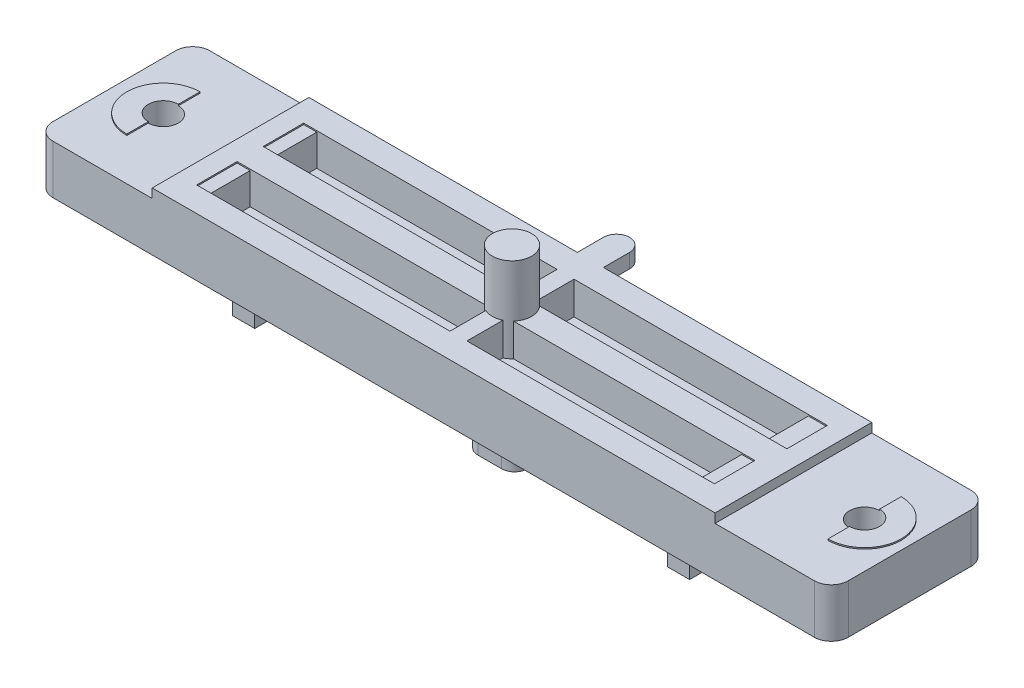
SolidWorks part; units mm, degrees
ref_plane "Alzado" through (0, 0, 0) normal (0, 0, 1) x (1, 0, 0)
ref_plane "Planta" through (0, 0, 0) normal (0, 1, 0) x (1, 0, 0)
ref_plane "Vista lateral" through (0, 0, 0) normal (1, 0, 0) x (0, 0, -1)
sketch "Croquis1" plane through (0, 0, 0) normal (0, 1, 0) x (1, 0, 0)
  line L0 (0, 0) -> (0, -12)
  line L1 (0, -12) -> (60.9, -12)
  line L2 (0, 0) -> (60.9, 0)
  line L3 (60.9, 0) -> (60.9, -12)
  dimension "D1" = 12
  dimension "D2" = 60.9
extrude "Saliente-Extruir1" add sketch "Croquis1" along normal blind 14
sketch "Croquis2" plane through (0, 14, 0) normal (0, 1, 0) x (1, 0, 0)
  line L0 (0, 0) -> (60.9, -12) construction
  circle A0 centre (30.45, -6) radius 1.5
  dimension "D1" = 3
extrude "Cortar-Extruir1" cut sketch "Croquis2" against normal blind 4 flip side to cut
sketch "Croquis3" plane through (0, 10, 0) normal (0, 1, 0) x (1, 0, 0)
  line L0 (30.45, -6) -> (30.45, 0) construction
  line L1 (60.9, 0) -> (0, 0) construction
  line L2 (30.45, 0) -> (29.45, 0)
  line L3 (29.45, 0) -> (29.45, 3)
  line L4 (29.45, 3) -> (31.45, 3)
  line L5 (31.45, 3) -> (31.45, 0)
  line L6 (31.45, 0) -> (30.45, 0)
  dimension "D1" = 1
  dimension "D2" = 2
  dimension "D3" = 3
extrude "Saliente-Extruir3" add sketch "Croquis3" against normal blind 1.1
sketch "Croquis4" plane through (0, 10, 0) normal (0, 1, 0) x (1, 0, 0)
  line L0 (30.45, -6) -> (8.9, -6) construction
  line L1 (8.9, -6) -> (8.9, 0)
  line L2 (29.45, 0) -> (0, 0) construction
  line L3 (8.9, 0) -> (29.45, 0)
  line L4 (60.9, 0) -> (31.45, 0) construction
  line L5 (52, 0) -> (52, -12)
  line L6 (0, -12) -> (60.9, -12) construction
  line L7 (52, -12) -> (8.9, -12)
  line L8 (8.9, -12) -> (8.9, -6)
  line L9 (29.45, 0) -> (29.45, 3)
  line L10 (29.45, 3) -> (31.45, 3)
  line L11 (31.45, 3) -> (31.45, 0)
  line L12 (31.45, 0) -> (52, 0)
  dimension "D1" = 21.55
  dimension "D2" = 43.1
extrude "Cortar-Extruir2" cut sketch "Croquis4" against normal blind 0.7 flip side to cut
sketch "Croquis5" plane through (0, 10, 0) normal (0, 1, 0) x (1, 0, 0)
  line L0 (52, -6) -> (49.5, -6) construction
  line L1 (52, -12) -> (52, 0) construction
  line L2 (49.05, -1.9) -> (49.05, -5)
  line L5 (49.05, -7) -> (49.05, -10.1)
  line L6 (49.05, -1.9) -> (31.1, -1.9)
  line L7 (49.05, -5) -> (31.568, -5)
  line L8 (49.05, -7) -> (31.568, -7)
  line L9 (49.05, -10.1) -> (31.1, -10.1)
  line L10 (30.45, -6) -> (30.45, -10.931) construction
  line L11 (31.1, -1.9) -> (31.1, -4.6481)
  line L12 (31.1, -7.3519) -> (31.1, -10.1)
  line L13 (29.8, -1.9) -> (11.4, -1.9)
  line L14 (11.4, -1.9) -> (11.4, -5)
  line L15 (11.4, -10.1) -> (29.8, -10.1)
  line L16 (29.332, -5) -> (11.4, -5)
  line L17 (8.9, 0) -> (8.9, -12) construction
  line L18 (11.4, -7) -> (29.332, -7)
  line L19 (11.4, -7) -> (11.4, -10.1)
  line L20 (29.8, -1.9) -> (29.8, -4.6481)
  line L21 (29.8, -7.3519) -> (29.8, -10.1)
  line L22 (30.45, -7) -> (31.568, -7)
  arc A0 (31.1, -7.3519) -> (31.568, -7) centre (30.45, -6) ccw
  arc A1 (31.568, -5) -> (31.1, -4.6481) centre (30.45, -6) ccw
  arc A2 (29.332, -7) -> (29.8, -7.3519) centre (30.45, -6) ccw
  arc A3 (31.1, -7.3519) -> (31.568, -7) centre (30.45, -6) ccw
  arc A4 (29.8, -4.6481) -> (29.332, -5) centre (30.45, -6) ccw
  arc A5 (31.568, -5) -> (31.1, -4.6481) centre (30.45, -6) ccw
  circle M22 centre (30.45, -6) radius 1.5
  dimension "D2" = 2.5
  dimension "D1" = 2.5
  dimension "D3" = 0.65
  dimension "D4" = 3.1
  dimension "D5" = 3.1
  dimension "D6" = 0.65
extrude "Cortar-Extruir3" cut sketch "Croquis5" against normal blind 2.5 contours L20 L13 L14 L16 M22 | L21 L18 L19 L15 M22 | L12 L9 L5 L8 M22 | L6 L11 L7 L2 M22 region at (40.0898, 10, 3.4476) region at (20.5851, 10, 3.4477) region at (40.0898, 10, 8.5524) region at (20.5851, 10, 8.5523)
sketch "Croquis6" plane through (0, 10, 0) normal (0, 1, 0) x (1, 0, 0)
  line L0 (49.05, -1.9) -> (50.5, -1.9)
  line L1 (49.05, -5) -> (50.5, -5)
  line L2 (50.5, -5) -> (50.5, -1.9)
  line L3 (52, -12) -> (52, 0) construction
  line L4 (49.05, -1.9) -> (49.05, -5)
  line L5 (50.05, -7) -> (50.05, -10.1)
  line L6 (11.4, -1.9) -> (10.4, -1.9)
  line L7 (49.05, -10.1) -> (49.05, -7)
  line L8 (49.05, -7) -> (50.05, -7)
  line L9 (49.05, -10.1) -> (50.05, -10.1)
  line L10 (10.4, -1.9) -> (10.4, -5)
  line L12 (11.4, -10.1) -> (11.4, -7)
  line L13 (8.9, 0) -> (8.9, -12) construction
  line L14 (11.4, -5) -> (10.4, -5)
  line L15 (11.4, -7) -> (10.4, -7)
  line L16 (11.4, -5) -> (11.4, -1.9)
  line L17 (10.4, -7) -> (10.4, -10.1)
  line L18 (11.4, -10.1) -> (10.4, -10.1)
  dimension "D1" = 1.5
  dimension "D2" = 1.5
extrude "Cortar-Extruir4" cut sketch "Croquis6" against normal blind 0.1
fillet "Redondeo1" radius 1 1 edges at (31.45, 9.45, -3)
fillet "Redondeo2" radius 1 1 edges at (29.45, 9.45, -3)
sketch "Croquis7" plane through (0, 9.3, 0) normal (0, 1, 0) x (1, 0, 0)
  line L0 (60.9, -6) -> (58.6, -6) construction
  line L1 (60.9, -12) -> (60.9, 0) construction
  line L2 (57.45, -8.8) -> (57.45, -7.15)
  line L3 (57.45, -4.85) -> (57.45, -3.2)
  line L6 (3.75, -4.85) -> (3.75, -3.2)
  line L7 (3.75, -7.15) -> (3.75, -8.8)
  arc A0 (57.45, -7.15) -> (57.45, -4.85) centre (57.45, -6) ccw
  arc A1 (57.45, -8.8) -> (57.45, -3.2) centre (57.45, -6) ccw
  arc A2 (3.75, -4.85) -> (3.75, -7.15) centre (3.75, -6) ccw
  arc A3 (3.75, -3.2) -> (3.75, -8.8) centre (3.75, -6) ccw
  dimension "D2" = 2.3
  dimension "D3" = 5.6
  dimension "D1" = 2.3
extrude "Saliente-Extruir4" add sketch "Croquis7" along normal blind 0.1 contours A3 L7 A2 L6 | A0 L3 A1 L2
sketch "Croquis8" plane through (0, 9.3, 0) normal (0, 1, 0) x (1, 0, 0)
  circle A0 centre (57.45, -6) radius 1.15
  circle A1 centre (3.75, -6) radius 1.15
extrude "Cortar-Extruir5" cut sketch "Croquis8" against normal up to next
sketch "Croquis9" plane through (0, 0, 0) normal (0, -1, 0) x (1, 0, 0)
  line L1 (30, 6) -> (30, 7.25)
  line L2 (30, 7.25) -> (28.1, 7.25)
  line L3 (28.1, 7.25) -> (28.1, 4.75)
  line L4 (28.1, 4.75) -> (31.9, 4.75)
  line L5 (31.9, 4.75) -> (31.9, 7.25)
  line L6 (31.9, 7.25) -> (30, 7.25)
  dimension "D1" = 1.9
  dimension "D2" = 1.25
  dimension "D3" = 3.8
  dimension "D4" = 2.5
extrude "Cortar-Extruir7" cut sketch "Croquis9" against normal blind 5.55 flip side to cut contours L2 L3 L4 L5 L6
sketch "Croquis10" plane through (0, 5.55, 0) normal (0, -1, 0) x (1, 0, 0)
  line L0 (29.35, 4.75) -> (30.65, 4.75)
  line L1 (31.9, 7.25) -> (28.1, 7.25) construction
  line L5 (45.8, 9.45) -> (45.8, 6.56) construction
  line L6 (30, 2.45) -> (47.5, 2.45)
  line L17 (14.2, 5.34) -> (14.2, 2.45) construction
  line L18 (29.35, 4.75) -> (29.35, 3.75)
  line L19 (29.35, 2.45) -> (30.65, 2.45)
  line L20 (30.65, 3.75) -> (30.65, 4.75)
  line L21 (28.1, 4.75) -> (29.35, 4.75)
  line L22 (30, 2.45) -> (12.5, 2.45)
  line L23 (47.5, 2.45) -> (47.5, 9.45)
  line L24 (14.2, 3.75) -> (29.35, 3.75)
  line L25 (12.5, 2.45) -> (12.5, 9.45)
  line L26 (12.5, 9.45) -> (14.2, 9.45)
  line L27 (47.5, 9.45) -> (45.8, 9.45)
  line L30 (30.65, 4.75) -> (31.9, 4.75)
  line L31 (30.65, 3.75) -> (45.8, 3.75)
  line L32 (14.2, 9.45) -> (14.2, 6.56) construction
  line L34 (45.8, 9.45) -> (45.8, 6.56)
  line L35 (14.2, 9.45) -> (14.2, 6.56)
  line L36 (15.8, 5.95) -> (15.8, 6.56)
  line L37 (15.8, 6.56) -> (14.2, 6.56)
  line L39 (14.2, 5.34) -> (15.8, 5.34)
  line L40 (15.8, 5.34) -> (15.8, 5.95)
  line L42 (44.2, 5.95) -> (44.2, 6.56)
  line L43 (44.2, 6.56) -> (45.8, 6.56)
  line L45 (45.8, 5.34) -> (44.2, 5.34)
  line L46 (44.2, 5.34) -> (44.2, 5.95)
  line L47 (45.8, 5.34) -> (45.8, 3.75)
  line L48 (14.2, 5.34) -> (14.2, 3.75)
  line L49 (45.8, 5.34) -> (45.8, 3.75) construction
  line M17 (31.9, 4.75) -> (28.1, 4.75)
  dimension "D1" = 3.3
  dimension "D2" = 1.3
  dimension "D3" = 4.8
  dimension "D4" = 17.5
  dimension "D5" = 17.5
  dimension "D6" = 1.3
  dimension "D7" = 7
  dimension "D8" = 1.7
  dimension "D9" = 0.61
  dimension "D11" = 3.3
  dimension "D12" = 0.61
extrude "Saliente-Extruir6" add sketch "Croquis10" along normal blind 3.5 contours L48 L39 L40 L36 L37 L35 L26 L25 L22 L19 L6 L23 L27 L34 L43 L42 L46 L45 L47 L31 L20 L18 L24 M17 region at (30, 5.55, 4.2479)
sketch "Croquis12" plane through (0, 2.05, 0) normal (0, -1, 0) x (1, 0, 0)
  line L0 (45.8, 3.75) -> (14.2, 3.75)
  line L1 (14.2, 3.75) -> (14.2, 2.45)
  line L2 (47.5, 2.45) -> (12.5, 2.45) construction
  line L3 (14.2, 2.45) -> (45.8, 2.45)
  line L4 (47.5, 2.45) -> (12.5, 2.45) construction
  line L5 (45.8, 2.45) -> (45.8, 3.75)
extrude "Cortar-Extruir8" cut sketch "Croquis12" against normal blind 2.3
sketch "Croquis14" plane through (0, 2.05, 0) normal (0, -1, 0) x (1, 0, 0)
  line L0 (29.35, 4.75) -> (30.65, 4.75)
  line L1 (30.65, 4.75) -> (30.65, 3.75)
  line L2 (30.65, 3.75) -> (29.35, 3.75)
  line L3 (29.35, 3.75) -> (29.35, 4.75)
extrude "Cortar-Extruir9" cut sketch "Croquis14" against normal blind 2.3
fillet "Redondeo3" radius 1 1 edges at (30, 4.35, 4.75)
sketch "Croquis15" plane through (0, 5.55, 0) normal (0, -1, 0) x (1, 0, 0)
  line L0 (59.6, 10.7) -> (59.6, 1.3)
  line L1 (51.98, 10.7) -> (59.6, 10.7)
  line L3 (59.6, 1.3) -> (51.98, 1.3)
  line L4 (60.9, 0) -> (60.9, 12) construction
  line L5 (0, 0) -> (60.9, 0) construction
  line L6 (60.9, 12) -> (0, 12) construction
  line L7 (51.98, 10.7) -> (51.98, 1.3)
  line L8 (1.3, 10.7) -> (1.3, 1.3)
  line L9 (8.9, 10.7) -> (1.3, 10.7)
  line L11 (1.3, 1.3) -> (8.9, 1.3)
  line L12 (8.9, 1.3) -> (8.9, 10.7)
  line L13 (0, 12) -> (0, 0) construction
  dimension "D1" = 1.3
  dimension "D2" = 1.3
  dimension "D3" = 1.3
  dimension "D4" = 7.62
  dimension "D5" = 1.3
  dimension "D6" = 1.3
  dimension "D7" = 1.3
  dimension "D8" = 7.6
extrude "Cortar-Extruir10" cut sketch "Croquis15" against normal blind 1.9
fillet "Redondeo4" radius 1.3 1 edges at (60.9, 7.425, 0)
fillet "Redondeo5" radius 1.3 3 edges at (0, 7.425, 0) (0, 7.425, 12) (60.9, 7.425, 12)
fillet "Redondeo6" radius 1.3 4 edges at (1.3, 6.5, 10.7) (1.3, 6.5, 1.3) (59.6, 6.5, 1.3) (59.6, 6.5, 10.7)
fillet "Redondeo7" radius 1 4 edges at (28.1, 2.775, 4.75) (28.1, 2.775, 7.25) (31.9, 2.775, 4.75) (31.9, 2.775, 7.25)
